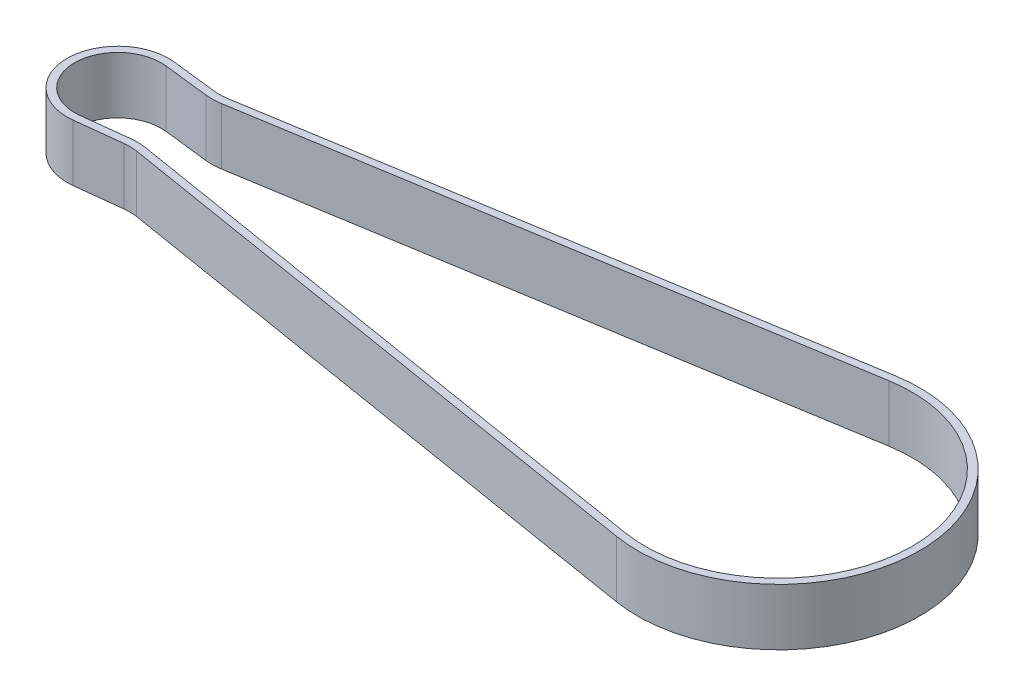
SolidWorks part; units mm, degrees
note: '?' marks a value the reader was unsure of.
ref_plane "Ebene vorne" through (0, 0, 0) normal (0, 0, 1) x (1, 0, 0)
ref_plane "Ebene oben" through (0, 0, 0) normal (0, 1, 0) x (1, 0, 0)
ref_plane "Ebene rechts" through (0, 0, 0) normal (1, 0, 0) x (0, 0, -1)
sketch "Skizze1" plane through (0, 0, 0) normal (0, 1, 0) x (1, 0, 0)
  line L0 (0.5488, -4.7434) -> (5.3564, -4.1871)
  line L1 (-12.3148, 0) -> (45.0363, 0) construction
  line L2 (0, 14.3488) -> (0, -8.3794) construction
  line L3 (67.5904, -14.1376) -> (6.9029, -4.2233)
  line L4 (67.5904, 14.1376) -> (6.9029, 4.2233)
  line L5 (0.5488, 4.7434) -> (5.3564, 4.1871)
  arc A0 (0.5488, 4.7434) -> (0.5488, -4.7434) centre (0, 0) ccw
  arc A1 (67.5904, -14.1376) -> (67.5904, 14.1376) centre (69.9, 0) ccw
  circle A2 centre (6, -9.75) radius 5.6 construction
  circle A3 centre (6, 9.75) radius 5.6 construction
  arc A4 (5.3564, -4.1871) -> (6.9029, -4.2233) centre (6, -9.75) cw
  arc A5 (5.3564, 4.1871) -> (6.9029, 4.2233) centre (6, 9.75) ccw
  dimension "D1" = 9.55
  dimension "D2" = 28.65
  dimension "D5" = 11.2
  dimension "D3" = 69.9
  dimension "D4" = 19.5
  dimension "D6" = 6
extrude "Linear-Austragen-Dünn1" add sketch "Skizze1" along normal blind 3 and the other way blind 3 thin
ref_axis "Achse1" through (0, -3.3, 0) along (0, 1, 0)?
ref_axis "Achse2" through (69.9, -3, 0) along (0, 1, 0)?
